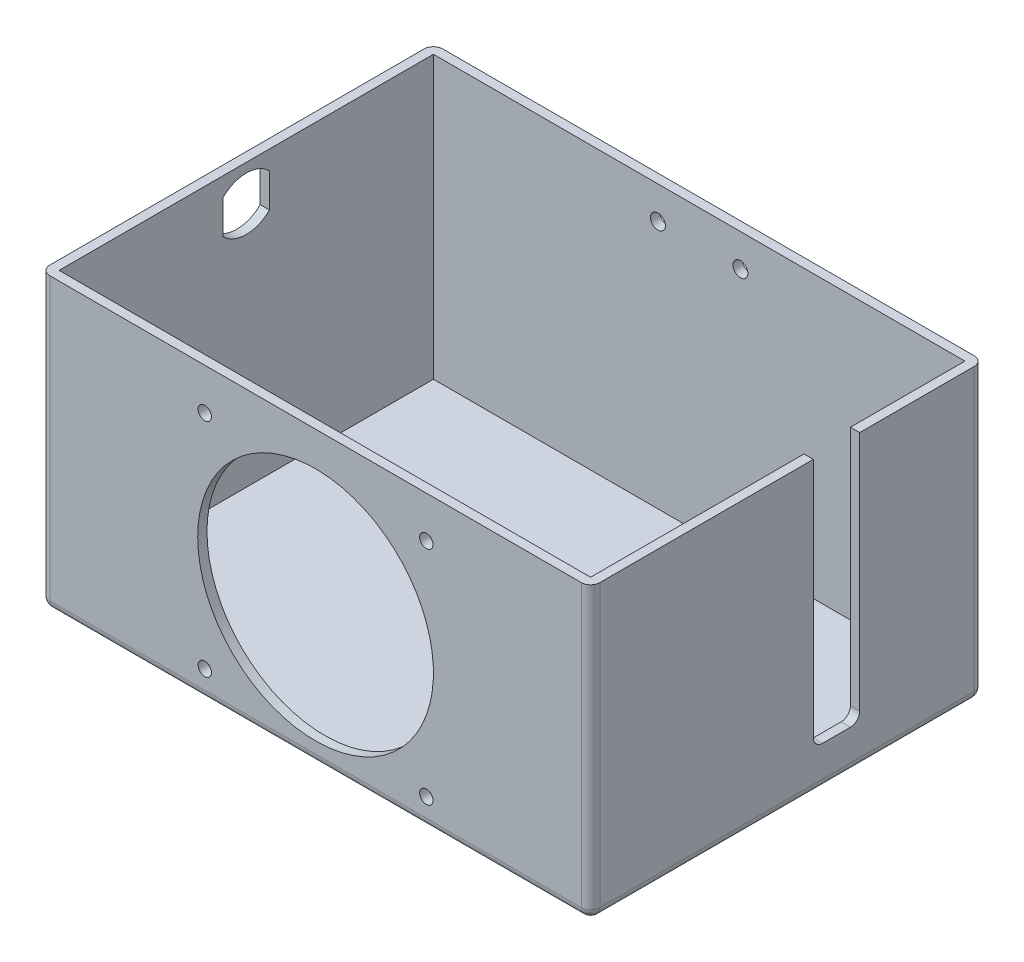
SolidWorks part; units mm, degrees
ref_plane "Front Plane" through (0, 0, 0) normal (0, 0, 1) x (1, 0, 0)
ref_plane "Top Plane" through (0, 0, 0) normal (0, 1, 0) x (1, 0, 0)
ref_plane "Right Plane" through (0, 0, 0) normal (1, 0, 0) x (0, 0, -1)
ref_plane "Plane1" through (0, 93.98, 0) normal (0, 1, 0) x (1, 0, 0)
sketch "Sketch1" plane through (0, 93.98, 0) normal (0, 1, 0) x (1, 0, 0)
  line L0 (-88.9, -63.5) -> (88.9, -63.5)
  line L1 (88.9, -63.5) -> (88.9, 63.5)
  line L2 (88.9, 63.5) -> (-88.9, 63.5)
  line L3 (-88.9, 63.5) -> (-88.9, -63.5)
extrude "Boss-Extrude1" add sketch "Sketch1" against normal blind 93.98
sketch "Sketch2" plane through (0, 93.98, 0) normal (0, 1, 0) x (-1, 0, 0)
  line L0 (85.9, 60.5) -> (-85.9, 60.5)
  line L1 (-85.9, 60.5) -> (-85.9, -60.5)
  line L2 (-85.9, -60.5) -> (85.9, -60.5)
  line L3 (85.9, -60.5) -> (85.9, 60.5)
extrude "Cut-Extrude1" cut sketch "Sketch2" against normal blind 90.98
sketch "Sketch3" plane through (85.9, 0, 0) normal (-1, 0, 0) x (0, 0, 1)
  line L0 (-23.5, 93.98) -> (-23.5, 13)
  line L1 (-23.5, 13) -> (-8.5, 13)
  line L2 (-8.5, 13) -> (-8.5, 93.98)
  line L3 (-8.5, 93.98) -> (-23.5, 93.98)
extrude "Cut-Extrude2" cut sketch "Sketch3" against normal through all
sketch "Sketch4" plane through (-85.9, 0, 0) normal (1, 0, 0) x (0, 0, -1)
  line L0 (7.5, 76.8734) -> (7.5, 87.8734)
  line L1 (-7.5, 87.8734) -> (-7.5, 76.8734)
  arc A0 (-7.5, 76.8734) -> (7.5, 76.8734) centre (0, 84.3734) ccw
  arc A1 (7.5, 87.8734) -> (-7.5, 87.8734) centre (0, 80.3734) ccw
extrude "Cut-Extrude3" cut sketch "Sketch4" against normal through all
hole_wizard "M4 Clearance Hole1" positions "Sketch6" profile "Sketch5" hole size "M4" standard "ANSI Metric"
sketch "Sketch6" plane through (0, 0, 60.5) normal (0, 0, -1) x (-1, 0, 0)
  point P0 (35.809, 80.604)
  point P1 (-35.809, 8.986)
  point P2 (35.809, 8.986)
  point P3 (-35.809, 80.604)
sketch "Sketch5" plane through (-35.809, 80.604, 60.5) normal (1, 0, 0) x (0, 1, 0)
  line L0 (0, 0) -> (0, 3)
  line L1 (0, 3) -> (2.159, 3)
  line L2 (2.159, 3) -> (2.159, 0)
  line L5 (2.159, 0) -> (0, 0)
  line L11 (0, -6.35) -> (0, 107.95) construction
  dimension "Thru Hole Dia." = 4.318
  dimension "Thru Hole Depth" = 3
hole_wizard "M72 Clearance Hole1" positions "Sketch8" profile "Sketch7" hole size "M72" standard "ANSI Metric"
sketch "Sketch8" plane through (0, 0, 60.5) normal (0, 0, -1) x (-1, 0, 0)
  point P0 (0, 44.795)
sketch "Sketch7" plane through (0, 44.795, 60.5) normal (1, 0, 0) x (0, 1, 0)
  line L0 (0, 0) -> (0, 3)
  line L1 (0, 3) -> (38.1, 3)
  line L2 (38.1, 3) -> (38.1, 0)
  line L5 (38.1, 0) -> (0, 0)
  line L11 (0, -6.35) -> (0, 107.95) construction
  dimension "Thru Hole Dia." = 76.2
  dimension "Thru Hole Depth" = 3
fillet "Fillet1" radius 3 10 edges at (88.9, 46.99, 63.5) (-88.9, 46.99, 63.5) (0, 0, 63.5) (-88.9, 46.99, -63.5) (88.9, 0, 0) (88.9, 46.99, -63.5) (-88.9, 0, 0) (0, 0, -63.5) (87.4, 13, -23.5) (87.4, 13, -8.5) tangent propagation no
sketch "Sketch9" plane through (0, 0, -63.5) normal (0, 0, -1) x (-1, 0, 0)
  line L0 (0, 0) -> (0, 93.98) construction
  line L1 (-19.05, 93.98) -> (19.05, 93.98)
  line L5 (55, 93.98) -> (-55, 93.98) construction
  circle A0 centre (-13.335, 83.439) radius 2.413
  circle A1 centre (13.335, 83.439) radius 2.413
  point P9 (0, 93.98)
  dimension "D5" = 4.826
extrude "Cut-Extrude4" cut sketch "Sketch9" against normal up to surface (3 mm away) contours A1 | A0 up to face at (0, 48.49, -60.5)
